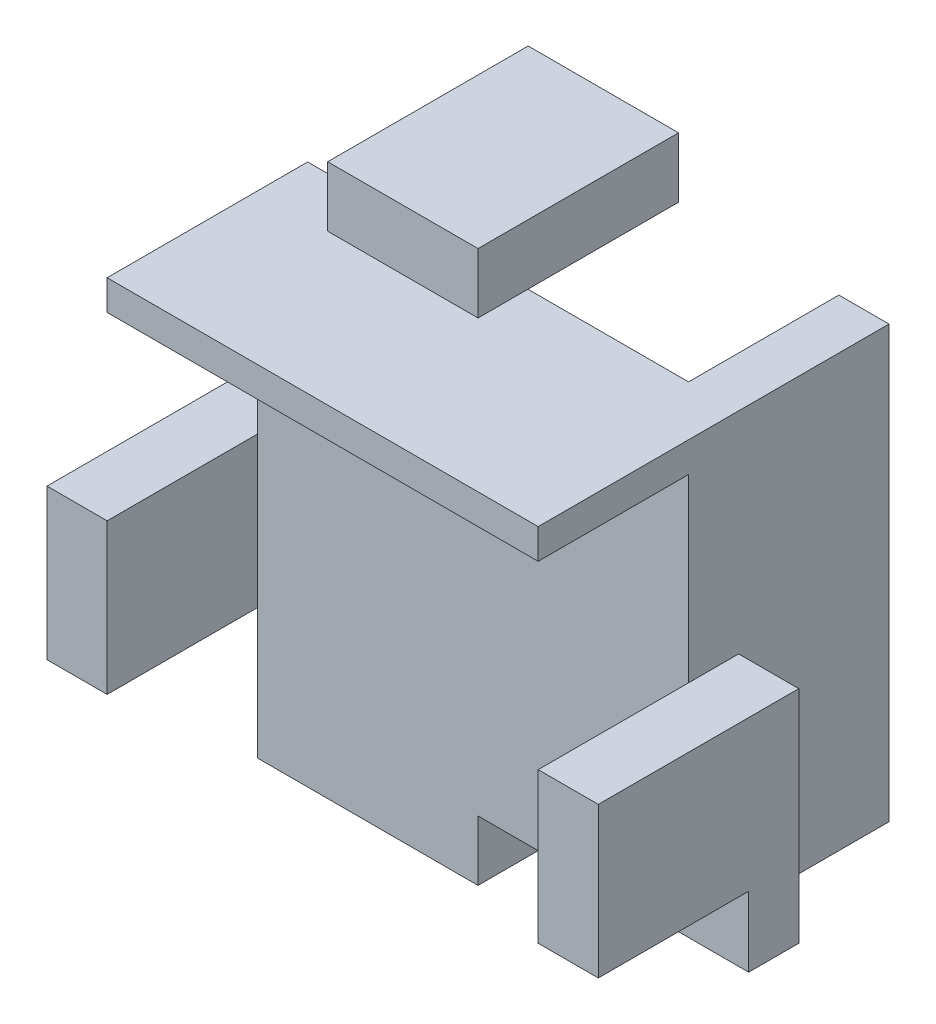
SolidWorks part; units mm, degrees
material "ABS"
ref_plane "前视基准面" through (0, 0, 0) normal (0, 0, 1) x (1, 0, 0)
ref_plane "上视基准面" through (0, 0, 0) normal (0, 1, 0) x (1, 0, 0)
ref_plane "右视基准面" through (0, 0, 0) normal (1, 0, 0) x (0, 0, -1)
sketch "草图1" plane through (0, 0, 0) normal (0, 0, 1) x (1, 0, 0)
  line L0 (-50.797, 9.0326) -> (-50.797, 3.0326)
  line L1 (-77.797, 31.0326) -> (-71.797, 31.0326)
  line L2 (-77.797, 31.0326) -> (-77.797, 9.0326)
  line L3 (-77.797, 9.0326) -> (-50.797, 9.0326)
  line L4 (-22.797, 31.0326) -> (-22.797, 9.0326)
  line L5 (-50.797, 58.0326) -> (-28.797, 58.0326)
  line L6 (-50.797, 58.0326) -> (-50.797, 52.0326)
  line L7 (-50.797, 3.0326) -> (-28.797, 3.0326)
  line L8 (-28.797, 58.0326) -> (-28.797, 31.0326)
  line L9 (-28.797, 9.0326) -> (-28.797, 3.0326)
  line L10 (-28.797, 9.0326) -> (-22.797, 9.0326)
  line L11 (-28.797, 31.0326) -> (-22.797, 31.0326)
  line L12 (-50.797, 49.0326) -> (-50.797, 31.0326)
  line L13 (-50.797, 9.0326) -> (-35.797, 9.0326)
  line L14 (-50.797, 9.0326) -> (-50.797, 3.0326)
  line L15 (-50.797, 3.0326) -> (-35.797, 3.0326)
  line L16 (-35.797, 9.0326) -> (-35.797, 3.0326)
  line L17 (-50.797, 52.0326) -> (-35.797, 52.0326)
  line L18 (-50.797, 52.0326) -> (-50.797, 58.0326)
  line L19 (-50.797, 58.0326) -> (-35.797, 58.0326)
  line L20 (-35.797, 52.0326) -> (-35.797, 58.0326)
  line L21 (-28.797, 31.0326) -> (-22.797, 31.0326)
  line L22 (-28.797, 31.0326) -> (-28.797, 16.0326)
  line L23 (-28.797, 16.0326) -> (-22.797, 16.0326)
  line L24 (-22.797, 31.0326) -> (-22.797, 16.0326)
  line L25 (-77.797, 31.0326) -> (-71.797, 31.0326)
  line L26 (-77.797, 31.0326) -> (-77.797, 16.0326)
  line L27 (-77.797, 16.0326) -> (-71.797, 16.0326)
  line L28 (-71.797, 31.0326) -> (-71.797, 16.0326)
  line L29 (-68.797, 9.0326) -> (-71.797, 9.0326)
  line L30 (-68.797, 9.0326) -> (-68.797, 49.0326)
  line L31 (-68.797, 49.0326) -> (-71.797, 49.0326)
  line L32 (-71.797, 9.0326) -> (-71.797, 49.0326)
  line L33 (-28.797, 49.0326) -> (-71.797, 49.0326)
  line L34 (-28.797, 49.0326) -> (-28.797, 52.0326)
  line L35 (-28.797, 52.0326) -> (-71.797, 52.0326)
  line L36 (-71.797, 49.0326) -> (-71.797, 52.0326)
  line L37 (-68.797, 31.0326) -> (-50.797, 31.0326)
  dimension "D1" = 55
  dimension "D2" = 22
  dimension "D3" = 55
  dimension "D4" = 22
  dimension "D5" = 6
  dimension "D6" = 6
  dimension "D7" = 15
  dimension "D8" = 6
  dimension "D9" = 15
  dimension "D10" = 15
  dimension "D11" = 6
  dimension "D12" = 15
  dimension "D13" = 3
  dimension "D14" = 40
extrude "拉伸-薄壁3" add sketch "草图1" along normal blind 15 thin contours L11 thin type one direction wall 15
extrude "凸台-拉伸3" add sketch "草图1<7>" along normal blind 15 separate body contours L28 L1 L2 L27 region at (-74.797, 23.5326, 0)
sketch "草图1<7>" plane through (0, 0, 0) normal (0, 0, 1) x (1, 0, 0) same geometry as "草图1"
extrude "凸台-拉伸4" add sketch "草图1<8>" along normal blind 15 separate body contours L36 L31 L33 L8 L35 L17 region at (-50.297, 50.5326, 0)
sketch "草图1<8>" plane through (0, 0, 0) normal (0, 0, 1) x (1, 0, 0) same geometry as "草图1"
extrude "凸台-拉伸5" add sketch "草图1<11>" against normal blind 5 contours L37 L30 L3 L13 L16 L7 L9 L10 L4 L23 L22 L8 L33 L12 | L30 L37 L12 L33 | L22 L23 L4 L11 | L28 L1 L2 L27 | L32 L3 L30 L31 L28 | L36 L31 L33 L8 L35 L17 | L17 L20 L5 L6 | L35 L8 L5 L20 | L16 L13 L0 L7 region at (-43.297, 6.0326, 0) region at (-44.9565, 25.1922, 0) region at (-70.297, 29.0326, 0) region at (-59.797, 40.0326, 0) region at (-74.797, 23.5326, 0) region at (-50.297, 50.5326, 0) region at (-25.797, 23.5326, 0) region at (-43.297, 55.0326, 0) region at (-32.297, 55.0326, 0)
sketch "草图1<11>" plane through (0, 0, 0) normal (0, 0, 1) x (1, 0, 0) same geometry as "草图1"
extrude "凸台-拉伸10" add sketch "草图1<13>" against normal blind 20 contours L32 L29 L30 L31
sketch "草图1<13>" plane through (0, 0, 0) normal (0, 0, 1) x (1, 0, 0) same geometry as "草图1"
sketch "草图3" plane through (0, 0, -5) normal (0, 0, -1) x (-1, 0, 0)
  line L0 (50.797, 58.0326) -> (28.797, 58.0326) construction
  line L1 (35.9279, 58.0326) -> (50.797, 58.0326)
  line L2 (35.9279, 58.0326) -> (35.9279, 52.0326)
  line L3 (35.9279, 52.0326) -> (50.797, 52.0326)
  line L4 (50.797, 58.0326) -> (50.797, 52.0326)
  line L5 (50.797, 3.0326) -> (28.797, 3.0326) construction
  line L6 (50.797, 9.0326) -> (35.9279, 9.0326)
  line L7 (50.797, 9.0326) -> (50.797, 3.0326)
  line L8 (50.797, 3.0326) -> (35.9279, 3.0326)
  line L9 (35.9279, 9.0326) -> (35.9279, 3.0326)
extrude "凸台-拉伸15" add sketch "草图3" along normal blind 15
sketch "草图4" plane through (0, 0, -5) normal (0, 0, -1) x (-1, 0, 0)
  line L2 (50.797, 52.0326) -> (28.797, 52.0326)
  line L3 (50.797, 52.0326) -> (50.797, 58.0326)
  line L4 (50.797, 58.0326) -> (28.797, 58.0326)
  line L5 (28.797, 52.0326) -> (28.797, 58.0326)
  line L6 (71.797, 52.0326) -> (64.797, 52.0326)
  line L7 (71.797, 52.0326) -> (71.797, 58.0326)
  line L8 (71.797, 58.0326) -> (64.797, 58.0326)
  line L9 (64.797, 52.0326) -> (64.797, 58.0326)
  dimension "D1" = 6
  dimension "D2" = 7
extrude "切除-拉伸2" cut sketch "草图4" against normal through all
sketch "草图8" plane through (0, 0, -20) normal (0, 0, -1) x (-1, 0, 0)
  line L0 (50.797, 58.0326) -> (35.9279, 58.0326) construction
  line L1 (35.9279, 58.0326) -> (50.797, 58.0326)
  line L2 (35.9279, 58.0326) -> (35.9279, 52.0326)
  line L3 (35.9279, 52.0326) -> (50.797, 52.0326)
  line L4 (50.797, 58.0326) -> (50.797, 52.0326)
  line L5 (35.9279, 58.0326) -> (35.9279, 52.0326) construction
extrude "切除-拉伸3" cut sketch "草图8" against normal through all
sketch "草图10" plane through (0, 0, 0) normal (0, 0, 1) x (1, 0, 0)
  line L0 (-71.797, 49.0326) -> (-71.797, 52.0326) construction
  line L1 (-64.797, 52.0532) -> (-49.797, 52.0532)
  line L2 (-64.797, 52.0532) -> (-64.797, 58.0532)
  line L3 (-64.797, 58.0532) -> (-49.797, 58.0532)
  line L4 (-49.797, 52.0532) -> (-49.797, 58.0532)
  dimension "D1" = 15
  dimension "D2" = 6
  dimension "D3" = 7
extrude "凸台-拉伸16" add sketch "草图10" against normal up to vertex (20 mm away) separate body up to point (-35.9279, 3.0326, -20)
sketch "草图13" plane through (0, 0, 0) normal (0, 0, 1) x (1, 0, 0)
  line L1 (-50.797, 9.0326) -> (-28.797, 9.0326)
  line L2 (-50.797, 9.0326) -> (-50.797, 3.0326)
  line L3 (-50.797, 3.0326) -> (-28.797, 3.0326)
  line L4 (-28.797, 9.0326) -> (-28.797, 3.0326)
extrude "切除-拉伸4" cut sketch "草图13" against normal through all
sketch "草图15" plane through (0, 0, 0) normal (0, 0, 1) x (1, 0, 0)
  line L1 (-71.797, 9.0326) -> (-64.797, 9.0326)
  line L2 (-71.797, 9.0326) -> (-71.797, 3.0326)
  line L3 (-71.797, 3.0326) -> (-64.797, 3.0326)
  line L4 (-64.797, 9.0326) -> (-64.797, 3.0326)
  line L5 (-64.797, 9.0326) -> (-49.797, 9.0326)
  line L6 (-64.797, 9.0326) -> (-64.797, 3.0326)
  line L7 (-64.797, 3.0326) -> (-49.797, 3.0326)
  line L8 (-49.797, 9.0326) -> (-49.797, 3.0326)
  dimension "D1" = 6
  dimension "D2" = 7
  dimension "D3" = 15
extrude "凸台-拉伸17" add sketch "草图15" against normal blind 5 contours L3 L4 L1 L2
sketch "草图16" plane through (0, 0, 0) normal (0, 0, 1) x (1, 0, 0)
  line L0 (-64.797, 9.0326) -> (-22.797, 9.0326) construction
  line L1 (-64.797, 3.0326) -> (-49.797, 3.0326)
  line L2 (-64.797, 3.0326) -> (-64.797, 9.0326)
  line L3 (-64.797, 9.0326) -> (-49.797, 9.0326)
  line L4 (-49.797, 3.0326) -> (-49.797, 9.0326)
  dimension "D1" = 15
extrude "凸台-拉伸18" add sketch "草图16" against normal up to vertex (20 mm away) up to point (-49.797, 52.0532, -20)
sketch "草图17" plane through (0, 0, -5) normal (0, 0, -1) x (-1, 0, 0)
  line L1 (68.797, 49.0326) -> (71.797, 49.0326)
  line L2 (68.797, 49.0326) -> (68.797, 9.0326)
  line L3 (68.797, 9.0326) -> (71.797, 9.0326)
  line L4 (71.797, 49.0326) -> (71.797, 9.0326)
extrude "切除-拉伸5" cut sketch "草图17" along normal through all contours L2 L3 L4 L1
sketch "草图18" plane through (0, 0, -5) normal (0, 0, -1) x (-1, 0, 0)
  line L0 (49.797, 9.0326) -> (22.797, 9.0326) construction
  line L1 (28.797, 52.0326) -> (33.797, 52.0326)
  line L2 (28.797, 52.0326) -> (28.797, 9.0326)
  line L3 (28.797, 9.0326) -> (33.797, 9.0326)
  line L4 (33.797, 52.0326) -> (33.797, 9.0326)
  dimension "D1" = 5
extrude "凸台-拉伸19" add sketch "草图18" along normal up to vertex (15 mm away) up to point (-49.797, 52.0532, -20)
